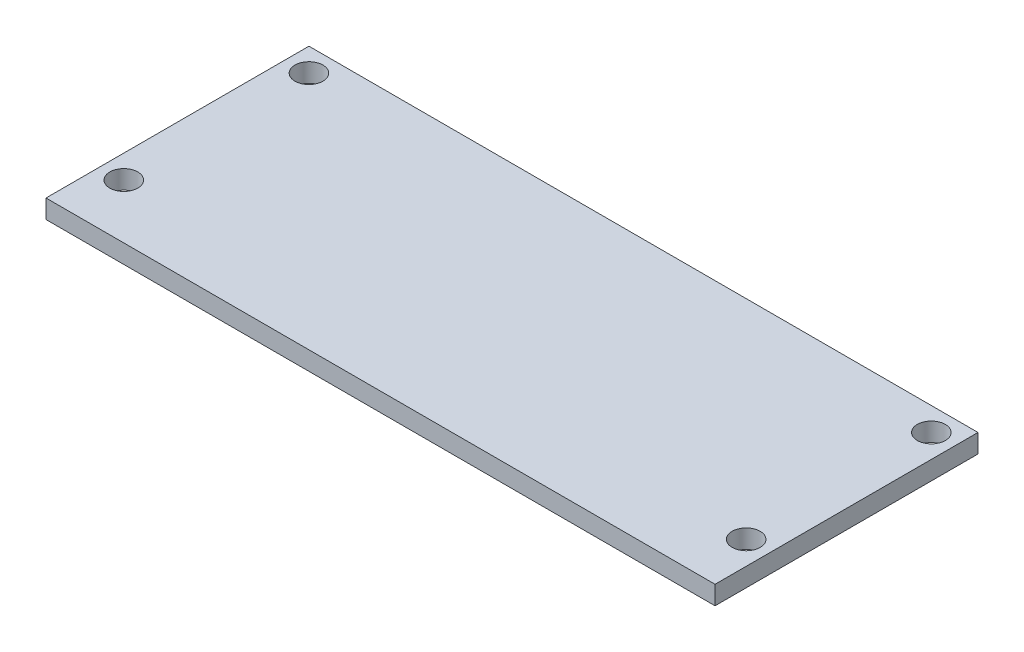
SolidWorks part; units mm, degrees
ref_plane "Front Plane" through (0, 0, 0) normal (0, 0, 1) x (1, 0, 0)
ref_plane "Top Plane" through (0, 0, 0) normal (0, 1, 0) x (1, 0, 0)
ref_plane "Right Plane" through (0, 0, 0) normal (1, 0, 0) x (0, 0, -1)
sketch "Sketch1" plane through (0, 0, 0) normal (0, 1, 0) x (1, 0, 0)
  line L0 (0, -169) -> (0, 0)
  line L1 (0, -169) -> (430, -169)
  line L2 (0, 0) -> (430, 0)
  line L3 (430, 0) -> (430, -169)
  dimension "D1" = 0
  dimension "D2" = 430
  dimension "D3" = 169
extrude "Boss-Extrude1" add sketch "Sketch1" along normal blind 12
sketch "Sketch2" plane through (0, 12, 0) normal (0, 1, 0) x (1, 0, 0)
  line L0 (430, 0) -> (0, 0) construction
  line L1 (0, 0) -> (0, -169) construction
  line L5 (215, 0) -> (215, -169) construction
  line L6 (0, -169) -> (430, -169) construction
  circle A0 centre (15, -15) radius 9
  circle A7 centre (15, -134) radius 9
  circle A8 centre (415, -134) radius 9
  circle A9 centre (415, -15) radius 9
  dimension "D3" = 18
  dimension "D4" = 15
  dimension "D6" = 18
  dimension "D1" = 15
  dimension "D2" = 15
  dimension "D5" = 35
extrude "Cut-Extrude1" cut sketch "Sketch2" against normal blind 12 contours A0 | A0 | A7 | A8 | A9 region at (15, 12, 15)
